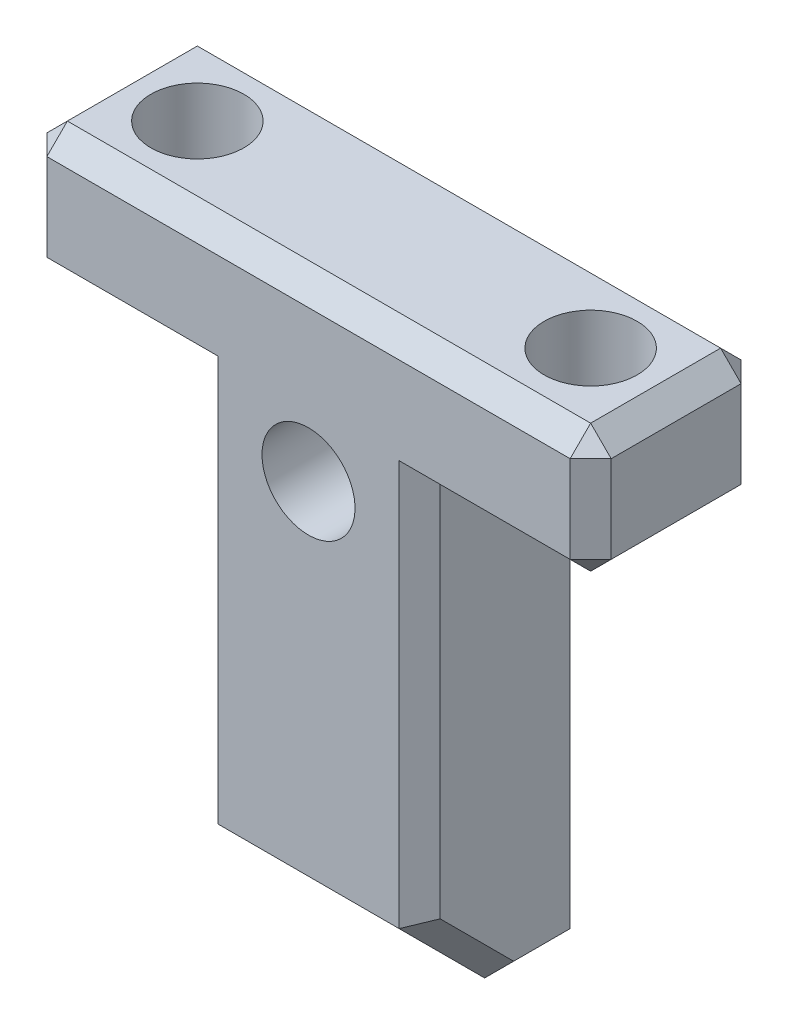
SolidWorks part; units mm, degrees
material "PET"
ref_plane "Front Plane" through (0, 0, 0) normal (0, 0, 1) x (1, 0, 0)
ref_plane "Top Plane" through (0, 0, 0) normal (0, 1, 0) x (1, 0, 0)
ref_plane "Right Plane" through (0, 0, 0) normal (1, 0, 0) x (0, 0, -1)
sketch "Sketch1" plane through (0, 0, 0) normal (0, 0, 1) x (1, 0, 0)
  line L1 (-59.8007, -22.225) -> (-51.5457, -22.225)
  line L2 (-59.8007, -22.225) -> (-59.8007, 0)
  line L3 (-59.8007, 0) -> (-51.5457, 0)
  line L4 (-51.5457, -22.225) -> (-51.5457, 0)
  point P4 (0, 0)
  dimension "D1" = 22.225
  dimension "D2" = 8.255
extrude "Boss-Extrude1" add sketch "Sketch1" along normal blind 6.35
sketch "Sketch2" plane through (-59.8007, 0, 0) normal (-1, 0, 0) x (0, 0, 1)
  line L0 (0, 0) -> (0, -22.225) construction
  line L1 (6.35, 0) -> (0, 0)
  line L2 (6.35, 0) -> (6.35, -4.7625)
  line L3 (6.35, -4.7625) -> (0, -4.7625)
  line L4 (0, 0) -> (0, -4.7625)
  dimension "D1" = 4.7625
extrude "Boss-Extrude2" add sketch "Sketch2" along normal blind 6.35
extrude "Boss-Extrude3" add sketch "Sketch2<4>" against normal blind 6.35 from surface contours L1 L4 L3 L2 starting at face at (-51.5457, -11.1125, 3.175)
sketch "Sketch2<4>" plane through (-59.8007, 0, 0) normal (-1, 0, 0) x (0, 0, 1) same geometry as "Sketch2"
hole_wizard "#4 Clearance Hole1" positions "Sketch3" profile "Sketch4" hole size "#4" standard "ANSI Inch" end condition through all
sketch "Sketch3" plane through (0, 0, 0) normal (0, 0, -1) x (-1, 0, 0)
  point P0 (55.6732, -6.35)
sketch "Sketch4" plane through (-55.6732, -6.35, 0) normal (1, 0, 0) x (0, 1, 0)
  line L0 (0, 0) -> (0, 6.35)
  line L1 (0, 6.35) -> (1.7272, 6.35)
  line L2 (1.7272, 6.35) -> (1.7272, 0)
  line L5 (1.7272, 0) -> (0, 0)
  line L11 (0, -6.35) -> (0, 107.95) construction
  dimension "Thru Hole Dia." = 3.4544
  dimension "Thru Hole Depth" = 6.35
hole_wizard "Hole1" positions "Sketch5" profile "Sketch6" legacy
sketch "Sketch5" plane through (0, 0, 0) normal (0, 0, -1) x (-1, 0, 0)
  point P0 (55.6732, -6.35)
sketch "Sketch6" plane through (-55.6732, -6.35, 0) normal (1, 0, 0) x (0, 1, 0)
  line L0 (0, 0) -> (0, 3.429)
  line L1 (0, 3.429) -> (1.9431, 3.429)
  line L2 (1.9431, 3.429) -> (2.0701, 0)
  line L3 (2.0701, 0) -> (0, 0)
  line L4 (0, 110) -> (0, -10) construction
  dimension "Minor Diameter" = 3.8862
  dimension "Depth" = 3.429
  dimension "Major Diameter" = 4.1402
hole_wizard "#4 Clearance Hole2" positions "Sketch7" profile "Sketch8" hole size "#4" standard "ANSI Inch" end condition through all
sketch "Sketch7" plane through (0, -4.7625, 0) normal (0, -1, 0) x (-1, 0, 0)
  line L0 (45.1957, 0) -> (51.5457, -6.35) construction
  line L1 (51.5457, -6.35) -> (66.1507, 0) construction
  line L2 (66.1507, 0) -> (59.8007, -6.35) construction
  point P12 (62.9757, -3.175)
  point P14 (48.3707, -3.175)
sketch "Sketch8" plane through (-48.3707, -4.7625, 3.175) normal (1, 0, 0) x (0, 0, -1)
  line L0 (0, 0) -> (0, 4.7625)
  line L1 (0, 4.7625) -> (1.7272, 4.7625)
  line L2 (1.7272, 4.7625) -> (1.7272, 0)
  line L5 (1.7272, 0) -> (0, 0)
  line L11 (0, -6.35) -> (0, 107.95) construction
  dimension "Thru Hole Dia." = 3.4544
  dimension "Thru Hole Depth" = 4.7625
chamfer "Chamfer1" distance 3.175 angle 45 1 edges at (-55.6732, -22.225, 6.35)
chamfer "Chamfer2" distance 0.762 angle 45 22 edges at (-48.3707, -4.7625, 6.35) (-48.3707, -4.7625, 0) (-51.5457, -13.4937, 0) (-51.5457, -22.225, 1.5875) (-51.5457, -20.6375, 4.7625) (-51.5457, -11.9062, 6.35) (-62.9757, -4.7625, 0) (-62.9757, -4.7625, 6.35) (-59.8007, -13.4937, 0) (-59.8007, -11.9062, 6.35) (-59.8007, -20.6375, 4.7625) (-59.8007, -22.225, 1.5875) (-55.6732, 0, 6.35) (-66.1507, -4.7625, 3.175) (-66.1507, -2.3813, 0) (-66.1507, -2.3813, 6.35) (-66.1507, 0, 3.175) (-55.6732, 0, 0) (-45.1957, -4.7625, 3.175) (-45.1957, -2.3812, 6.35) (-45.1957, 0, 3.175) (-45.1957, -2.3813, 0)
